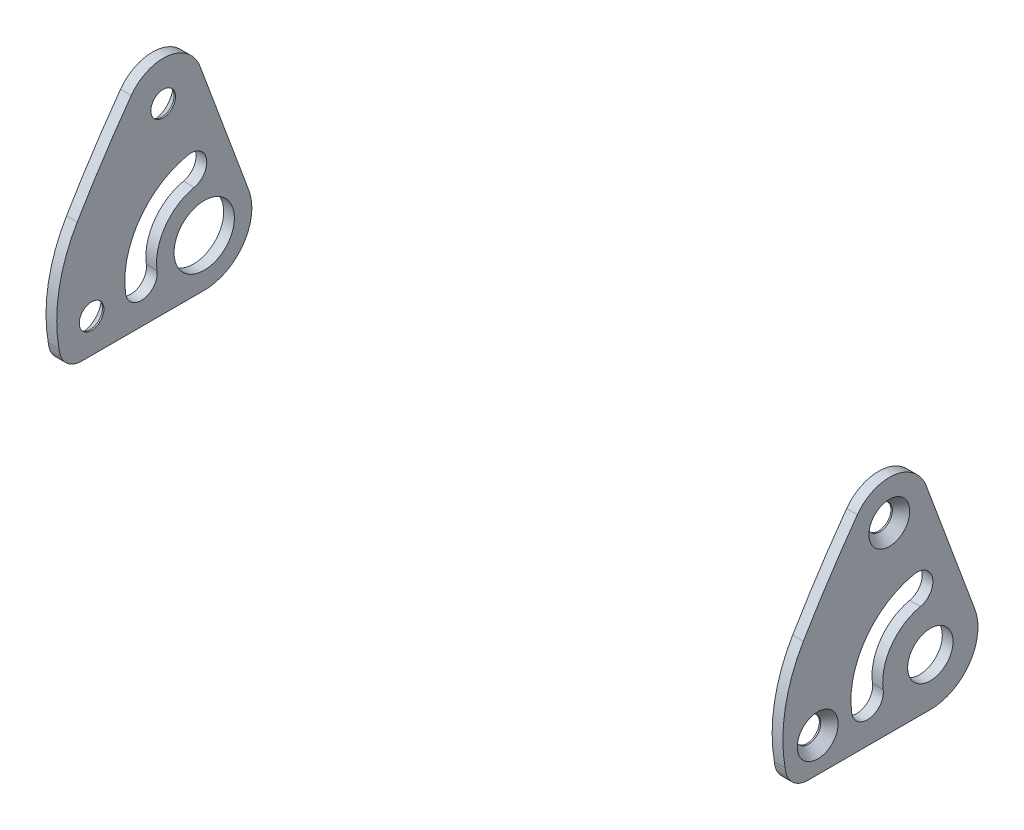
SolidWorks part; units mm, degrees
material "Ti-6Al-4VSolution treated and aged (SS)"
ref_plane "Front Plane" through (0, 0, 0) normal (0, 0, 1) x (1, 0, 0)
ref_plane "Top Plane" through (0, 0, 0) normal (0, 1, 0) x (1, 0, 0)
ref_plane "Right Plane" through (0, 0, 0) normal (1, 0, 0) x (0, 0, -1)
sketch "Sketch1" plane through (50.05, 0, 0) normal (1, 0, 0) x (0, 0, -1)
  line L1 (-163.3043, 20.32) -> (-154.1497, 20.32) construction
  line L2 (-171.4659, 20.32) -> (-151.65, 20.32)
  line L4 (-171.4659, 20.32) -> (-171.9734, 23.4009)
  line L6 (-145.3974, 29.3029) -> (-155.6745, 57.0553)
  arc A1 (-169.4172, 37.4866) -> (-155.6745, 57.0553) centre (-38.2131, -40.0455) cw
  circle A2 centre (-151.65, 26.9875) radius 4.2227
  arc A4 (-140.1251, 73.2669) -> (-169.4172, 37.4866) centre (-38.2131, -40.0455) ccw construction
  arc A6 (-171.97, -24.13) -> (-171.9734, 23.4009) centre (-306.6951, -0.3743) ccw construction
  arc A7 (-151.65, 20.32) -> (-145.3974, 29.3029) centre (-151.65, 26.9875) ccw
  arc A9 (-169.4172, 37.4866) -> (-171.9734, 23.4009) centre (-151.65, 26.9875) ccw construction
  arc A10 (-169.4172, 37.4866) -> (-171.9734, 23.4009) centre (-151.65, 26.9875) ccw
  arc A12 (-152.2224, 47.7331) -> (-161.8632, 49.041) centre (-157.3912, 45.8191) ccw
  dimension "D1" = 8.4455
  dimension "D2" = 5.5118
  dimension "D3" = 69.68
extrude "Boss-Extrude1" add sketch "Sketch1" along normal blind 1.5 contours L6 A12 A1 L2 A7 A2 region at (50.05, 33.7415, 159.4751)
sketch "Sketch2" plane through (51.55, 0, 0) normal (1, 0, 0) x (0, 0, -1)
  line L4 (-161.5796, 23.495) -> (-166.5679, 23.495) construction
  line L6 (-151.3256, 36.1685) -> (-153.5891, 42.2809) construction
  line L9 (-145.3974, 29.3029) -> (-152.2224, 47.7331) construction
  line L10 (-171.4659, 20.32) -> (-151.65, 20.32) construction
  arc A9 (-151.65, 20.32) -> (-145.3974, 29.3029) centre (-151.65, 26.9875) ccw construction
  arc A12 (-153.0484, 33.5067) -> (-158.2491, 26.035) centre (-151.65, 26.9875) ccw
  arc A16 (-153.9807, 37.8528) -> (-162.6485, 25.4) centre (-151.65, 26.9875) ccw
  arc A18 (-153.0484, 33.5067) -> (-153.9807, 37.8528) centre (-153.5146, 35.6798) ccw
  arc A19 (-158.2491, 26.035) -> (-162.6485, 25.4) centre (-160.4488, 25.7175) cw
  dimension "D1" = 3.175
  dimension "D2" = 3.175
  dimension "D3" = 11.1125
extrude "Cut-Extrude1" cut sketch "Sketch2" against normal up to next and the other way through all contours L6 A16 L4 A12 region at (51.55, 31.4145, 158.0102)
fillet "Fillet3" radius 3.175 1 edges at (50.8, 20.32, 171.4659)
hole_wizard "CSK for #4 Flat Head Machine Screw1" positions "Sketch4" profile "Sketch6" countersink size "#4" standard "ANSI Inch" end condition up to next
sketch "Sketch4" plane through (51.55, 0, 0) normal (1, 0, 0) x (0, 0, -1)
  line L0 (-168.7712, 20.32) -> (-151.65, 20.32) construction
  arc A0 (-152.2224, 47.7331) -> (-161.8632, 49.041) centre (-157.3912, 45.8191) ccw construction
  circle A1 centre (-167.4103, 25.0825) radius 4.7625 construction
  arc A4 (-153.9807, 37.8528) -> (-162.6485, 25.4) centre (-151.65, 26.9875) ccw construction
  point P0 (-167.4103, 25.0825)
  point P3 (-157.3912, 45.8191)
sketch "Sketch6" plane through (51.55, 25.0825, 167.4103) normal (0, 1, 0) x (0, 0, -1)
  line L0 (0, 0) -> (0, 1.5)
  line L1 (0, 1.5) -> (1.7272, 1.5)
  line L2 (1.7272, 1.5) -> (1.7272, 1.3003)
  line L3 (1.7272, 1.3003) -> (2.8575, 0)
  line L5 (2.8575, 0) -> (0, 0)
  line L6 (-1.7272, 1.3003) -> (-2.8575, 0) construction
  line L11 (0, -6.35) -> (0, 107.95) construction
  dimension "Thru Hole Dia." = 3.4544
  dimension "Thru Hole Depth" = 1.5
  dimension "Near C'Sink Dia." = 5.715
  dimension "Near C'Sink Angle" = 82
mirror "Mirror2" about plane through (0, 0, 0) normal (1, 0, 0) of bodies 110 101
sketch "Sketch7" plane through (51.55, 0, 0) normal (1, 0, 0) x (0, 0, -1)
  circle A0 centre (-151.65, 26.9875) radius 4.2227 construction
  circle A1 centre (-151.65, 26.9875) radius 4.2227
  circle A2 centre (-151.65, 26.9875) radius 3.175
  dimension "D1" = 6.35
extrude "Boss-Extrude2" add sketch "Sketch7" against normal up to surface (1.5 mm away) up to face at (50.05, 25.0825, 165.6831)
equation "\"weapon shaft threads\"= 5 / 16"
equation "\"D1@Sketch1\"=\"weapon shaft threads\" + .02in"
equation "\"D1@Boss-Extrude1\"=1.5mm"
